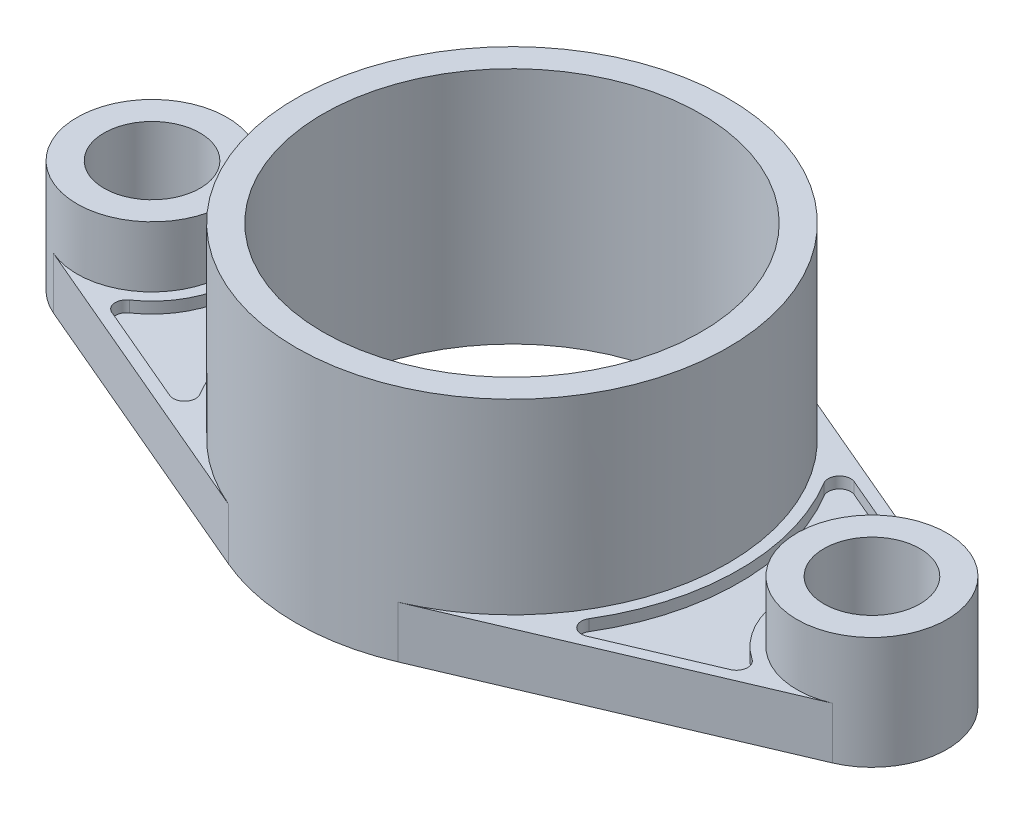
SolidWorks part; units mm, degrees
material "Polybutadiene (PB)"
ref_plane "Front Plane" through (0, 0, 0) normal (0, 0, 1) x (1, 0, 0)
ref_plane "Top Plane" through (0, 0, 0) normal (0, 1, 0) x (1, 0, 0)
ref_plane "Right Plane" through (0, 0, 0) normal (1, 0, 0) x (0, 0, -1)
sketch "Sketch1" plane through (0, 0, 0) normal (0, 1, 0) x (1, 0, 0)
  line L0 (-86.5278, 15.3351) -> (-18.8, 44.1651)
  line L1 (-86.5278, -15.3351) -> (-18.8, -44.1651)
  line L2 (86.5278, 15.3351) -> (18.8, 44.1651)
  line L3 (86.5278, -15.3351) -> (18.8, -44.1651)
  line L4 (0, 0) -> (-80, 0) construction
  circle A0 centre (0, 0) radius 48
  circle A1 centre (-80, 0) radius 10.6667
  circle A2 centre (80, 0) radius 10.6667
  circle A3 centre (-80, 0) radius 16.6667
  circle A4 centre (80, 0) radius 16.6667
  circle A5 centre (0, 0) radius 42
  dimension "D2" = 21.3333
  dimension "D3" = 96
  dimension "D4" = 33.3333
  dimension "D1" = 160
  dimension "D5" = 6
extrude "Boss-Extrude1" add sketch "Sketch1" along normal blind 11.5 contours A3 A1 | L4 A0 L0 A3 | A0 L4 A3 L1 | A4 L2 A0 L3 | A4 A2 | A5 A0 region at (-54.8023, 0, -17.8948) region at (-71.0681, 0, -13.5095) region at (0, 0, -46.6424) region at (-54.8023, 0, 17.8948) region at (54.8023, 0, 0) region at (93.5095, 0, -8.9319)
extrude "Boss-Extrude2" add sketch "Sketch1<3>" along normal blind 25 contours A3 A1 | A4 A2 region at (-71.0681, 0, -13.5095) region at (93.5095, 0, -8.9319)
sketch "Sketch1<3>" plane through (0, 0, 0) normal (0, 1, 0) x (1, 0, 0) same geometry as "Sketch1"
extrude "Boss-Extrude3" add sketch "Sketch1<4>" along normal blind 53 contours A5 A0 region at (0, 0, -46.6424)
sketch "Sketch1<4>" plane through (0, 0, 0) normal (0, 1, 0) x (1, 0, 0) same geometry as "Sketch1"
sketch "Sketch2" plane through (0, 11.5, 0) normal (0, 1, 0) x (1, 0, 0)
  line L4 (-73.6701, -18.0912) -> (-37.9794, -33.2839)
  line L5 (-37.9794, 33.2839) -> (-73.6701, 18.0912)
  line L6 (-68.7498, -20.1857) -> (-46.3293, -29.7295)
  line L7 (-46.3293, 29.7295) -> (-68.7498, 20.1857)
  arc A2 (-46.3293, -29.7295) -> (-43.211, -26.1354) centre (-45.3501, -27.4293) ccw
  arc A3 (-68.7498, -20.1857) -> (-69.1817, -15.8217) centre (-67.7707, -17.8854) cw
  arc A4 (-37.9794, 33.2839) -> (-37.9794, -33.2839) centre (0, 0) ccw
  arc A5 (-73.6701, -18.0912) -> (-73.6701, 18.0912) centre (-80, 0) ccw
  arc A6 (-43.211, 26.1354) -> (-43.211, -26.1354) centre (0, 0) ccw
  arc A7 (-69.1817, -15.8217) -> (-69.1817, 15.8217) centre (-80, 0) ccw
  arc A8 (-43.211, 26.1354) -> (-46.3293, 29.7295) centre (-45.3501, 27.4293) ccw
  arc A9 (-68.7498, 20.1857) -> (-69.1817, 15.8217) centre (-67.7707, 17.8854) ccw
  dimension "D2" = 2.5
  dimension "D1" = 2.5
extrude "Cut-Extrude1" cut sketch "Sketch2" against normal blind 2.5
mirror "Mirror1" about plane through (0, 0, 0) normal (1, 0, 0) of "Cut-Extrude1"
equation "\"A\"= 32"
equation "\"B\"= 6"
equation "\"C\"= 2.5"
equation "\"D1@Sketch1\"=\"A\"*5"
equation "\"D2@Sketch1\"=\"A\"*2/3"
equation "\"D3@Sketch1\"=\"A\"*3"
equation "\"D4@Sketch1\"=\"D2@Sketch1\"+2*\"B\""
equation "\"D5@Sketch1\"=\"B\""
equation "\"D1@Sketch2\"=\"C\""
equation "\"D2@Sketch2\"=\"C\""
equation "\"D1@Cut-Extrude1\"=\"C\""
equation "\"D1@Boss-Extrude1\"=9+\"C\""
